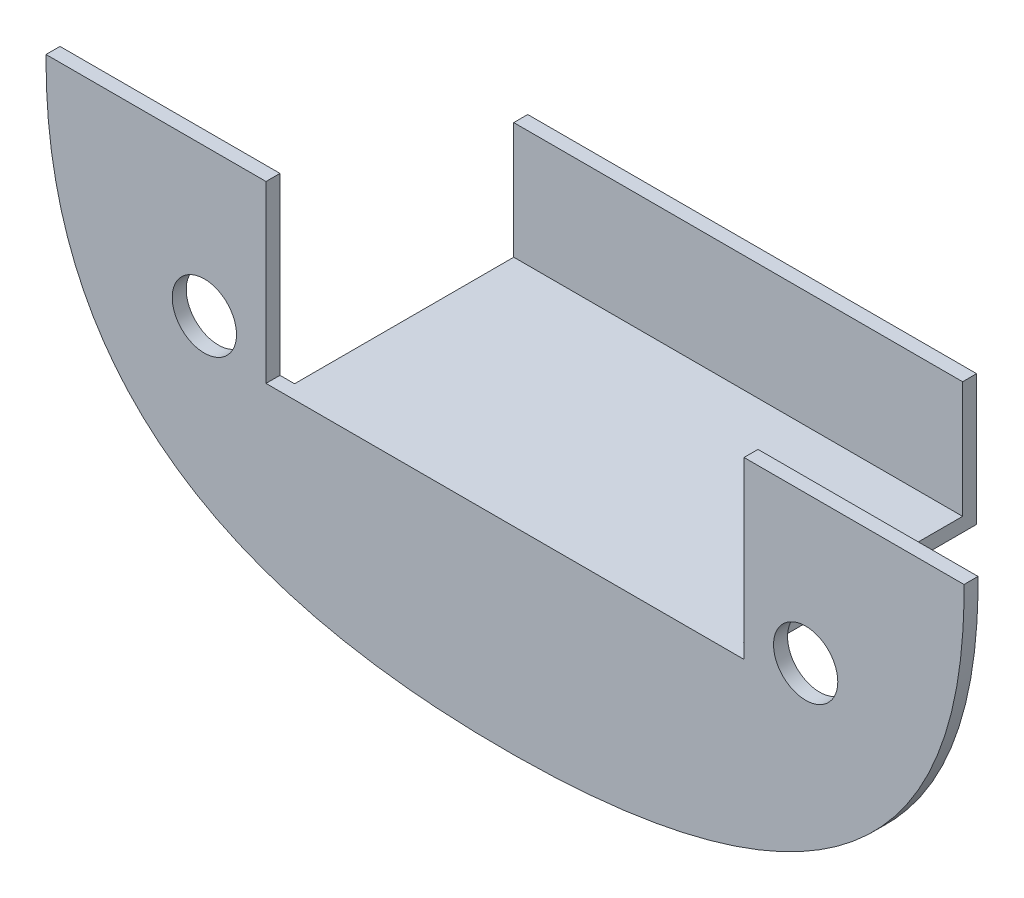
SolidWorks part; units mm, degrees
ref_plane "Front Plane" through (0, 0, 0) normal (0, 0, 1) x (1, 0, 0)
ref_plane "Top Plane" through (0, 0, 0) normal (0, 1, 0) x (1, 0, 0)
ref_plane "Right Plane" through (0, 0, 0) normal (1, 0, 0) x (0, 0, -1)
sketch "Sketch1" plane through (65.5, -188.8754, 24.4234) normal (0, 0, -1) x (-1, 0, 0)
  line L2 (-52.07, -36.8878) -> (52.07, -36.8878)
  line L3 (-52.07, -36.8878) -> (-42.5, -36.8878) construction
  line L4 (42.5, -36.8878) -> (52.07, -36.8878) construction
  line L5 (52.07, -36.8878) -> (52.07, 67.2522) construction
  line L6 (-52.07, -36.8878) -> (-52.07, 67.2522) construction
  line L7 (-52.07, -36.8878) -> (-42.5, -36.8878) construction
  line L8 (42.5, -36.8878) -> (52.07, -36.8878) construction
  line L9 (52.07, -36.8878) -> (52.07, 67.2522) construction
  line L10 (-52.07, -36.8878) -> (-52.07, 67.2522) construction
  line L11 (52.07, -36.8878) -> (52.07, 1.2122)
  line L12 (52.07, 1.2122) -> (100, 1.2122)
  line L13 (-100, 1.2122) -> (-52.07, 1.2122)
  line L14 (-52.07, 1.2122) -> (-52.07, -36.8878)
  circle A0 centre (-65.5, -30.8878) radius 7 construction
  circle A1 centre (-65.5, -30.8878) radius 7
  circle A4 centre (65.5, -30.8878) radius 7 construction
  circle A5 centre (65.5, -30.8878) radius 7
  spline S1 degree 3 poles (-100, 91.6667) (-100, 100.5541) (-99.8835, 101.663) (-99.344, 103.2464) (-98.4974, 104.6847) (-97.0622, 106.3843) (-94.8888, 108.1258) (-91.9976, 109.7782) (-88.9551, 111.1271) (-85.8262, 112.2552) (-82.6425, 113.2169) (-79.4227, 114.0479) (-76.1777, 114.7739) (-72.9147, 115.4129) (-69.6383, 115.979) (-65.2561, 116.6501) (-59.7591, 117.3544) (-53.1437, 118.032) (-46.5161, 118.5751) (-37.6683, 119.1501) (-26.5955, 119.6359) (-13.2992, 119.9414) (-4.4331, 120) (4.4331, 120) (13.2992, 119.9414) (26.5955, 119.6359) (37.6683, 119.1501) (46.5161, 118.5751) (53.1437, 118.032) (59.7591, 117.3544) (65.2561, 116.6501) (69.6383, 115.979) (72.9147, 115.4129) (76.1777, 114.7739) (79.4227, 114.0479) (82.6425, 113.2169) (85.8262, 112.2552) (88.9551, 111.1271) (91.9976, 109.7782) (94.8888, 108.1258) (97.0622, 106.3843) (98.4974, 104.6847) (99.344, 103.2464) (99.8835, 101.663) (100, 100.5541) (100, 91.6667) (100, 75) (100, 50) (100, 25) (100, 8.3333) (100, -3.0509) (99.7823, -9.1535) (98.6814, -18.2496) (96.6708, -27.1928) (93.6177, -35.841) (89.4261, -44.0037) (84.0794, -51.4648) (77.6729, -58.0369) (70.3884, -63.6161) (62.4486, -68.1997) (51.2385, -73.0758) (36.4788, -77.1218) (18.3084, -79.5568) (6.1019, -80) (-6.1019, -80) (-18.3084, -79.5568) (-36.4788, -77.1218) (-51.2385, -73.0758) (-62.4486, -68.1997) (-70.3884, -63.6161) (-77.6729, -58.0369) (-84.0794, -51.4648) (-89.4261, -44.0037) (-93.6177, -35.841) (-96.6708, -27.1928) (-98.6814, -18.2496) (-99.7823, -9.1535) (-100, -3.0509) (-100, 8.3333) (-100, 25) (-100, 50) (-100, 75) (-100, 91.6667) (-100, 100.5541) (-99.8835, 101.663) knots -0.070853 -0.035426 0 0 0.002356 0.004712 0.007067 0.009423 0.014135 0.018847 0.023558 0.02827 0.032982 0.037693 0.042405 0.047116 0.051828 0.05654 0.065963 0.075386 0.08481 0.094233 0.11308 0.131926 0.150773 0.150773 0.169619 0.188466 0.207313 0.216736 0.226159 0.235583 0.245006 0.249718 0.254429 0.259141 0.263853 0.268564 0.273276 0.277988 0.282699 0.287411 0.292123 0.294478 0.296834 0.29919 0.301546 0.301546 0.336972 0.372399 0.407825 0.443252 0.443252 0.456222 0.469192 0.482162 0.495132 0.508102 0.521072 0.534042 0.547012 0.559982 0.572952 0.598893 0.624833 0.650773 0.650773 0.676713 0.702653 0.728593 0.741563 0.754533 0.767504 0.780474 0.793444 0.806414 0.819384 0.832354 0.845324 0.858294 0.858294 0.893721 0.929147 0.964574 1 1 1.002356 1.004712 1.007067 only from (-100, 100) to (-100, 100)
  spline S2 degree 3 poles (-100, 91.6667) (-100, 100.5541) (-99.8835, 101.663) (-99.344, 103.2464) (-98.4974, 104.6847) (-97.0622, 106.3843) (-94.8888, 108.1258) (-91.9976, 109.7782) (-88.9551, 111.1271) (-85.8262, 112.2552) (-82.6425, 113.2169) (-79.4227, 114.0479) (-76.1777, 114.7739) (-72.9147, 115.4129) (-69.6383, 115.979) (-65.2561, 116.6501) (-59.7591, 117.3544) (-53.1437, 118.032) (-46.5161, 118.5751) (-37.6683, 119.1501) (-26.5955, 119.6359) (-13.2992, 119.9414) (-4.4331, 120) (4.4331, 120) (13.2992, 119.9414) (26.5955, 119.6359) (37.6683, 119.1501) (46.5161, 118.5751) (53.1437, 118.032) (59.7591, 117.3544) (65.2561, 116.6501) (69.6383, 115.979) (72.9147, 115.4129) (76.1777, 114.7739) (79.4227, 114.0479) (82.6425, 113.2169) (85.8262, 112.2552) (88.9551, 111.1271) (91.9976, 109.7782) (94.8888, 108.1258) (97.0622, 106.3843) (98.4974, 104.6847) (99.344, 103.2464) (99.8835, 101.663) (100, 100.5541) (100, 91.6667) (100, 75) (100, 50) (100, 25) (100, 8.3333) (100, -3.0509) (99.7823, -9.1535) (98.6814, -18.2496) (96.6708, -27.1928) (93.6177, -35.841) (89.4261, -44.0037) (84.0794, -51.4648) (77.6729, -58.0369) (70.3884, -63.6161) (62.4486, -68.1997) (51.2385, -73.0758) (36.4788, -77.1218) (18.3084, -79.5568) (6.1019, -80) (-6.1019, -80) (-18.3084, -79.5568) (-36.4788, -77.1218) (-51.2385, -73.0758) (-62.4486, -68.1997) (-70.3884, -63.6161) (-77.6729, -58.0369) (-84.0794, -51.4648) (-89.4261, -44.0037) (-93.6177, -35.841) (-96.6708, -27.1928) (-98.6814, -18.2496) (-99.7823, -9.1535) (-100, -3.0509) (-100, 8.3333) (-100, 25) (-100, 50) (-100, 75) (-100, 91.6667) (-100, 100.5541) (-99.8835, 101.663) knots -0.070853 -0.035426 0 0 0.002356 0.004712 0.007067 0.009423 0.014135 0.018847 0.023558 0.02827 0.032982 0.037693 0.042405 0.047116 0.051828 0.05654 0.065963 0.075386 0.08481 0.094233 0.11308 0.131926 0.150773 0.150773 0.169619 0.188466 0.207313 0.216736 0.226159 0.235583 0.245006 0.249718 0.254429 0.259141 0.263853 0.268564 0.273276 0.277988 0.282699 0.287411 0.292123 0.294478 0.296834 0.29919 0.301546 0.301546 0.336972 0.372399 0.407825 0.443252 0.443252 0.456222 0.469192 0.482162 0.495132 0.508102 0.521072 0.534042 0.547012 0.559982 0.572952 0.598893 0.624833 0.650773 0.650773 0.676713 0.702653 0.728593 0.741563 0.754533 0.767504 0.780474 0.793444 0.806414 0.819384 0.832354 0.845324 0.858294 0.858294 0.893721 0.929147 0.964574 1 1 1.002356 1.004712 1.007067 only from (-100, 100) to (-100, 100)
  point P17 (0, 0)
  dimension "D1" = 38.1
extrude "Boss-Extrude2" add sketch "Sketch1" along normal blind 3.048 contours L13 L12 L11 L2 L14 A1 A5 region at (65.5, -230.692, 24.4234)
sketch "Sketch2" plane through (0, 0, 21.3754) normal (0, 0, -1) x (-1, 0, 0)
  line L0 (-117.57, -225.7632) -> (-13.43, -225.7632) construction
  line L1 (-114.395, -225.7632) -> (-16.605, -225.7632)
  line L2 (-114.395, -225.7632) -> (-114.395, -228.8112)
  line L3 (-114.395, -228.8112) -> (-16.605, -228.8112)
  line L4 (-16.605, -225.7632) -> (-16.605, -228.8112)
  line L5 (-117.57, -187.6632) -> (-117.57, -225.7632) construction
  line L6 (-13.43, -225.7632) -> (-13.43, -187.6632) construction
  point P8 (-16.605, -227.2872)
  dimension "D1" = 3.175
  dimension "D2" = 3.175
  dimension "D3" = 3.048
extrude "Boss-Extrude3" add sketch "Sketch2" along normal blind 50.8
sketch "Sketch3" plane through (0, -225.7632, 0) normal (0, 1, 0) x (1, 0, 0)
  line L0 (114.395, 29.4246) -> (114.395, -21.3754) construction
  line L1 (16.605, 29.4246) -> (114.395, 29.4246)
  line L2 (16.605, 29.4246) -> (16.605, 26.3766)
  line L3 (16.605, 26.3766) -> (114.395, 26.3766)
  line L4 (114.395, 29.4246) -> (114.395, 26.3766)
  dimension "D1" = 3.048
extrude "Boss-Extrude4" add sketch "Sketch3" along normal blind 25.4
